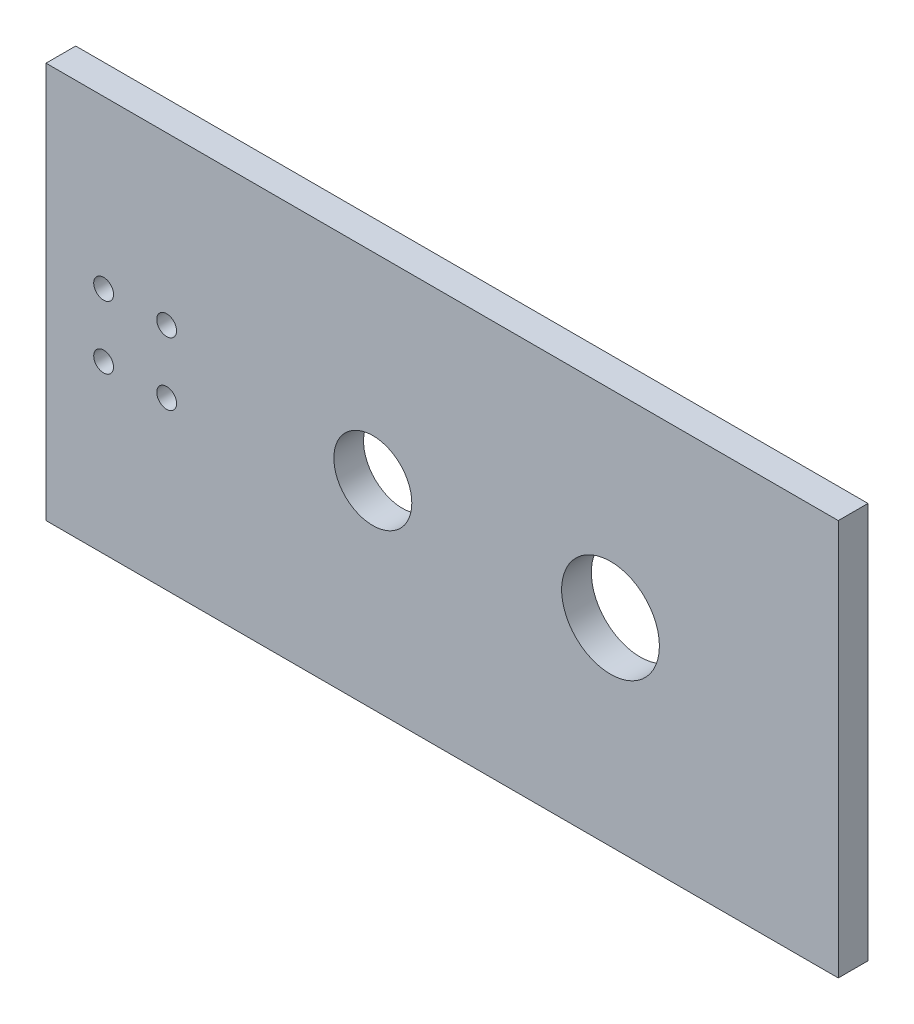
SolidWorks part; units mm, degrees
ref_plane "Front Plane" through (0, 0, 0) normal (0, 0, 1) x (1, 0, 0)
ref_plane "Top Plane" through (0, 0, 0) normal (0, 1, 0) x (1, 0, 0)
ref_plane "Right Plane" through (0, 0, 0) normal (1, 0, 0) x (0, 0, -1)
sketch "Sketch1" plane through (0, 0, 0) normal (0, 0, 1) x (1, 0, 0)
  line L1 (0, 0) -> (80, 0)
  line L2 (0, 0) -> (0, 40)
  line L3 (0, 40) -> (80, 40)
  line L4 (80, 0) -> (80, 40)
  dimension "D1" = 80
  dimension "D2" = 40
extrude "Boss-Extrude1" add sketch "Sketch1" along normal blind 3 contours L3 L4 L1 L2
sketch "Sketch2" plane through (0, 0, 3) normal (0, 0, 1) x (1, 0, 0)
  line L0 (0, 20) -> (80, 20) construction
  line L1 (0, 0) -> (0, 40) construction
  line L2 (80, 0) -> (80, 40) construction
  line L3 (9, 20) -> (13.5, 20) construction
  line L4 (4.318, 15.318) -> (13.682, 15.318) construction
  line L5 (4.318, 15.318) -> (4.318, 24.682) construction
  line L6 (4.318, 24.682) -> (13.682, 24.682) construction
  line L7 (13.682, 15.318) -> (13.682, 24.682) construction
  line L8 (4.318, 15.318) -> (13.682, 24.682) construction
  line L9 (4.318, 24.682) -> (13.682, 15.318) construction
  circle A1 centre (33, 20) radius 3.9365
  circle A2 centre (57, 20) radius 4.9365
  circle A3 centre (12.182, 23.182) radius 1
  circle A4 centre (9, 20) radius 4.5 construction
  circle A5 centre (12.182, 16.818) radius 1
  circle A6 centre (5.818, 16.818) radius 1
  circle A7 centre (5.818, 23.182) radius 1
  point P6 (9, 20)
  dimension "D1" = 9
  dimension "D2" = 7.873
  dimension "D3" = 9.873
  dimension "D5" = 2
  dimension "D7" = 9
  dimension "D4" = 24
  dimension "D6" = 24
  dimension "D8" = 1.5
extrude "Cut-Extrude1" cut sketch "Sketch2" against normal through all contours A1 L0 | L0 A1 | A2 L0 | L0 A2 | A7 | A3 | A5 | A6
